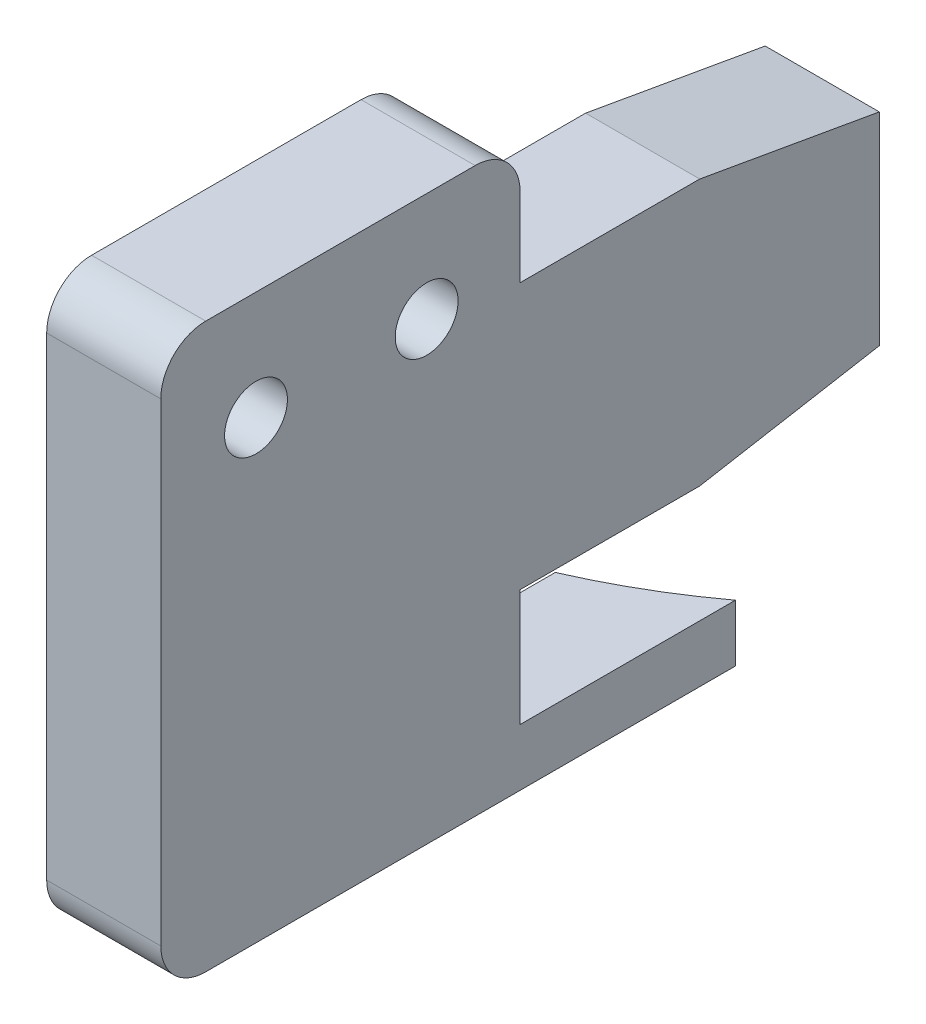
SolidWorks part; units mm, degrees
material "ABS"
ref_plane "Front Plane" through (0, 0, 0) normal (0, 0, 1) x (1, 0, 0)
ref_plane "Top Plane" through (0, 0, 0) normal (0, 1, 0) x (1, 0, 0)
ref_plane "Right Plane" through (0, 0, 0) normal (1, 0, 0) x (0, 0, -1)
sketch "Sketch1" plane through (0, 0, 0) normal (1, 0, 0) x (0, 0, -1)
  line L1 (-20, 19.4375) -> (20, 19.4375)
  line L2 (-20, 19.4375) -> (-20, -19.4375)
  line L3 (-20, -19.4375) -> (20, -19.4375)
  line L4 (20, 19.4375) -> (20, -19.4375)
  line L5 (20, -16.2625) -> (0, -16.2625)
  line L6 (20, -16.2625) -> (20, -9.7625)
  line L7 (20, -9.7625) -> (0, -9.7625)
  line L8 (0, -16.2625) -> (0, -9.7625)
  line L9 (20, 5.0375) -> (0, 5.0375)
  line L10 (20, 5.0375) -> (20, 11.5375)
  line L11 (20, 11.5375) -> (0, 11.5375)
  line L12 (0, 5.0375) -> (0, 11.5375)
  line L13 (0, 11.5375) -> (20, 11.5375)
  line L14 (0, 11.5375) -> (0, 19.4375)
  line L15 (0, 19.4375) -> (20, 19.4375)
  line L16 (20, 11.5375) -> (20, 19.4375)
  point P12 (-20, 0)
  dimension "D1" = 3.175
  dimension "D2" = 6.5
  dimension "D3" = 27.8
  dimension "D4" = 6.5
  dimension "D5" = 40
  dimension "D6" = 20
  dimension "D7" = 38.875
extrude "Boss-Extrude1" add sketch "Sketch1" along normal blind 6.353 contours L9 L12 L11 L4 L1 L2 L3 L5 L8 L7 region at (0, -1.6119, 3.6763)
sketch "Sketch2" plane through (6.353, 0, 0) normal (1, 0, 0) x (0, 0, -1)
  line L0 (-20, 19.4375) -> (0, 19.4375) construction
  line L1 (-20, 19.4375) -> (-20, -19.4375) construction
  line L2 (0, 5.0375) -> (0, 19.4375) construction
  line L3 (-20, 19.4375) -> (0, 19.4375)
  line L4 (-20, 19.4375) -> (-20, 11.9375)
  line L5 (-20, 11.9375) -> (0, 11.9375)
  line L6 (0, 19.4375) -> (0, 11.9375)
  circle A0 centre (-14.7, 5.8875) radius 1.75
  circle A1 centre (-5.2, 5.8875) radius 1.75
  dimension "D2" = 3.5
  dimension "D1" = 13.55
  dimension "D3" = 9.5
  dimension "D4" = 5.3
  dimension "D5" = 7.5
extrude "Cut-Extrude1" cut sketch "Sketch2" against normal up to next
sketch "Sketch3" plane through (0, -19.4375, 0) normal (0, -1, 0) x (1, 0, 0)
  line L0 (6.353, 20) -> (0, 20) construction
  circle A0 centre (-13, -38.1) radius 32.5
  dimension "D3" = 65
  dimension "D1" = 13
  dimension "D2" = 58.1
extrude "Cut-Extrude2" cut sketch "Sketch3" against normal up to surface (9.675 mm away) up to face at (3.1765, -9.7625, -10)
fillet "Fillet1" radius 2.5 3 edges at (3.1765, 11.9375, 0) (3.1765, -19.4375, 20) (3.1765, 11.9375, 20)
chamfer "Chamfer1" distance 10 angle 10 1 edges at (3.1765, 5.0375, -20) first distance on face at (3.1765, 5.0375, -10)
chamfer "Chamfer2" distance 10 angle 10 1 edges at (3.1765, -9.7625, -20) first distance on face at (3.1765, -9.7625, -10)
